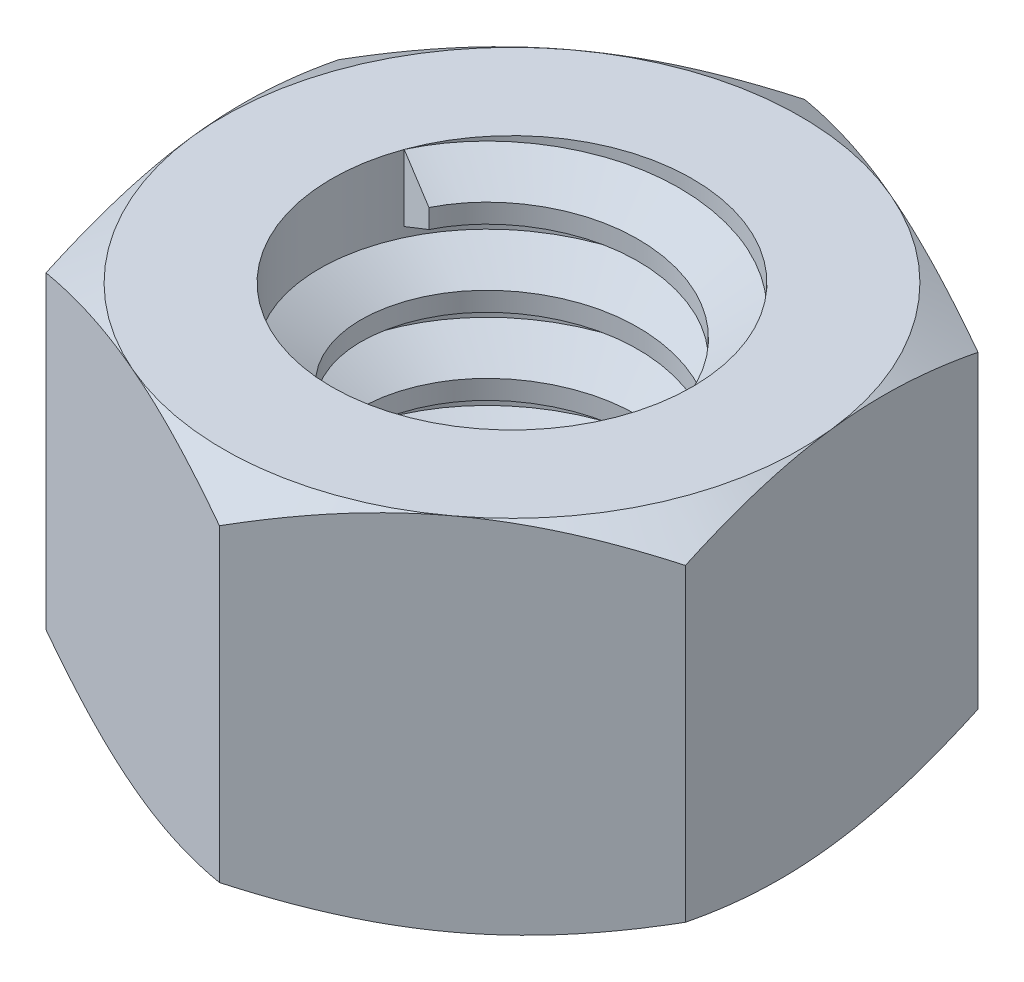
SolidWorks part; units mm, degrees
ref_plane "Front Plane" through (0, 0, 0) normal (0, 0, 1) x (1, 0, 0)
ref_plane "Top Plane" through (0, 0, 0) normal (0, 1, 0) x (1, 0, 0)
ref_plane "Right Plane" through (0, 0, 0) normal (1, 0, 0) x (0, 0, -1)
sketch "Szkic1" plane through (0, 0, 0) normal (0, 1, 0) x (1, 0, 0)
  line L1 (3.7081, 2.7538) -> (-0.5308, 4.5882)
  line L2 (-0.5308, 4.5882) -> (-4.2389, 1.8344)
  line L3 (-4.2389, 1.8344) -> (-3.7081, -2.7538)
  line L4 (-3.7081, -2.7538) -> (0.5308, -4.5882)
  line L5 (0.5308, -4.5882) -> (4.2389, -1.8344)
  line L6 (4.2389, -1.8344) -> (3.7081, 2.7538)
  circle A0 centre (0, 0) radius 4 construction
extrude "Dodanie-wyciągnięcie1" add sketch "Szkic1" along normal blind 5
sketch "Szkic2" plane through (0, 5, 0) normal (0, 1, 0) x (1, 0, 0)
  circle A0 centre (0, 0) radius 4
extrude "Wytnij-wyciągnięcie1" cut sketch "Szkic2" against normal blind 1 draft 60 flip side to cut
sketch "Szkic3" plane through (0, 0, 0) normal (0, -1, 0) x (1, 0, 0)
  circle A0 centre (0, 0) radius 4
extrude "Wytnij-wyciągnięcie2" cut sketch "Szkic3" against normal blind 1 draft 60 flip side to cut
sketch "Szkic4" plane through (0, 5, 0) normal (0, 1, 0) x (1, 0, 0)
  circle A0 centre (0, 0) radius 2.5
  dimension "D1" = 5
extrude "Wytnij-wyciągnięcie3" cut sketch "Szkic4" against normal blind 5
thread "Gwint1" pitch 1.0583 method extrude profile "Profil gwintu1" start angle 20, offset 0, length 4, pitch 1.0583, diameter 5
ref_plane "Płaszczyzna1" through (-2.3492, 5, -0.8551) normal (-0.342, 0, 0.9397) x (-0.9397, 0, -0.342)
sketch "Profil gwintu1" plane through (-2.3492, 5, -0.8551) normal (-0.342, 0, 0.9397) x (-0.9397, 0, -0.342)
  line L0 (0, 0) -> (0, 1.0583) construction
  line L11 (0, 0) -> (0, 0.926)
  line L12 (0, 0.926) -> (-0.5728, 0.5953)
  line L13 (-0.5728, 0.5953) -> (-0.5728, 0.3307)
  line L15 (-0.5728, 0.3307) -> (0, 0)
  line L17 (-0.5728, 0.463) -> (0, 0.463) construction
  point P2 (0, 0)
  dimension "Pitch" = 1.0583
  dimension "Profile_Angle" = 60
  dimension "Profile_Land" = 0.2646
  dimension "Profile_Height" = 0.5728
